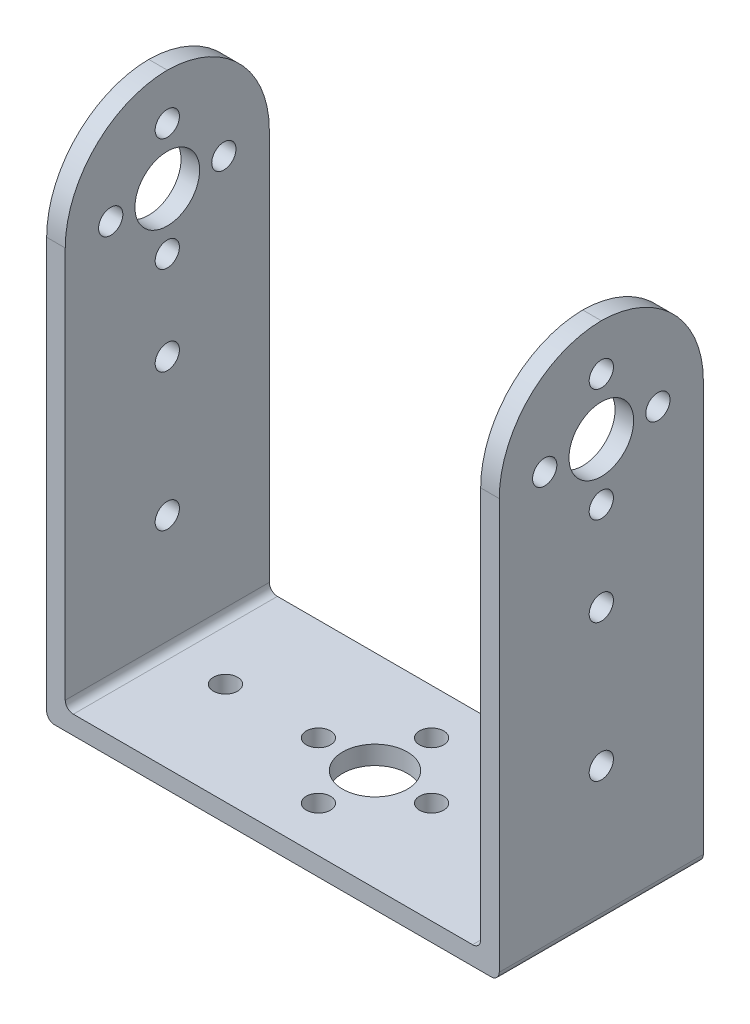
SolidWorks part; units mm, degrees
ref_plane "Front Plane" through (0, 0, 0) normal (0, 0, 1) x (1, 0, 0)
ref_plane "Top Plane" through (0, 0, 0) normal (0, 1, 0) x (1, 0, 0)
ref_plane "Right Plane" through (0, 0, 0) normal (1, 0, 0) x (0, 0, -1)
sketch "Sketch1" plane through (0, 0, 0) normal (0, 0, 1) x (1, 0, 0)
  line L1 (-28, 32.25) -> (28, 32.25)
  line L2 (-28, 32.25) -> (-28, -32.25)
  line L3 (-28, -32.25) -> (28, -32.25)
  line L4 (28, 32.25) -> (28, -32.25)
  line L5 (-28, 32.25) -> (28, -32.25) construction
  line L6 (-28, -32.25) -> (28, 32.25) construction
  point P0 (0, 0)
  dimension "D1" = 56
  dimension "D2" = 64.5
extrude "Boss-Extrude1" add sketch "Sketch1" along normal blind 25.25
sketch "Sketch2" plane through (0, 0, 25.25) normal (0, 0, 1) x (1, 0, 0)
  line L0 (28, 32.25) -> (-28, 32.25) construction
  line L1 (-25.7, 32.25) -> (25.7, 32.25)
  line L2 (-25.7, 32.25) -> (-25.7, -29.95)
  line L3 (-25.7, -29.95) -> (25.7, -29.95)
  line L4 (25.7, 32.25) -> (25.7, -29.95)
  line L5 (-28, 32.25) -> (-28, -32.25) construction
  line L6 (-28, -32.25) -> (28, -32.25) construction
  line L7 (28, -32.25) -> (28, 32.25) construction
  dimension "D1" = 2.3
  dimension "D2" = 2.3
  dimension "D3" = 2.3
extrude "Cut-Extrude1" cut sketch "Sketch2" against normal through all
fillet "Fillet1" radius 1 4 edges at (-28, -32.25, 12.625) (28, -32.25, 12.625) (25.7, -29.95, 12.625) (-25.7, -29.95, 12.625)
fillet "Fillet3" radius 12.75 4 edges at (-26.85, 32.25, 25.25) (26.85, 32.25, 25.25) (-26.85, 32.25, 0) (26.85, 32.25, 0)
sketch "Sketch4" plane through (0, -32.25, 0) normal (0, -1, 0) x (1, 0, 0)
  line L0 (0, 16.625) -> (0, 8.625) construction
  line L2 (-27, 0) -> (27, 0) construction
  line L4 (-4, 12.625) -> (4, 12.625) construction
  line L6 (28, 25.25) -> (28, 0) construction
  circle A0 centre (0, 12.625) radius 4
  circle A1 centre (7, 12.625) radius 1.5
  circle A2 centre (-7, 12.625) radius 1.5
  circle A3 centre (0, 5.625) radius 1.5
  circle A4 centre (0, 19.625) radius 1.5
  circle A5 centre (18.5, 12.625) radius 1.5
  circle A6 centre (-18.5, 12.625) radius 1.5
  point P7 (28, 12.625)
  dimension "D1" = 8
  dimension "D2" = 3
  dimension "D3" = 7
  dimension "D4" = 7
  dimension "D5" = 7
  dimension "D6" = 7
  dimension "D7" = 12.625
  dimension "D8" = 28
  dimension "D9" = 11.5
  dimension "D10" = 11.5
extrude "Cut-Extrude3" cut sketch "Sketch4" against normal through all
sketch "Sketch5" plane through (-28, 0, 0) normal (-1, 0, 0) x (0, 0, 1)
  line L2 (0, 19.5) -> (0, -31.25) construction
  circle A0 centre (12.625, 19.5494) radius 4
  circle A1 centre (12.625, 26.5494) radius 1.5
  circle A2 centre (19.625, 19.5494) radius 1.5
  circle A3 centre (12.625, 12.5494) radius 1.5
  circle A4 centre (5.625, 19.5494) radius 1.5
  circle A5 centre (12.625, 1.5494) radius 1.5
  circle A6 centre (12.625, -15.4506) radius 1.5
  dimension "D1" = 8
  dimension "D3" = 3
  dimension "D2" = 12.625
  dimension "D4" = 7
  dimension "D5" = 7
  dimension "D6" = 7
  dimension "D7" = 7
  dimension "D8" = 12.7
  dimension "D9" = 18
  dimension "D10" = 17
extrude "Cut-Extrude4" cut sketch "Sketch5" against normal through all
